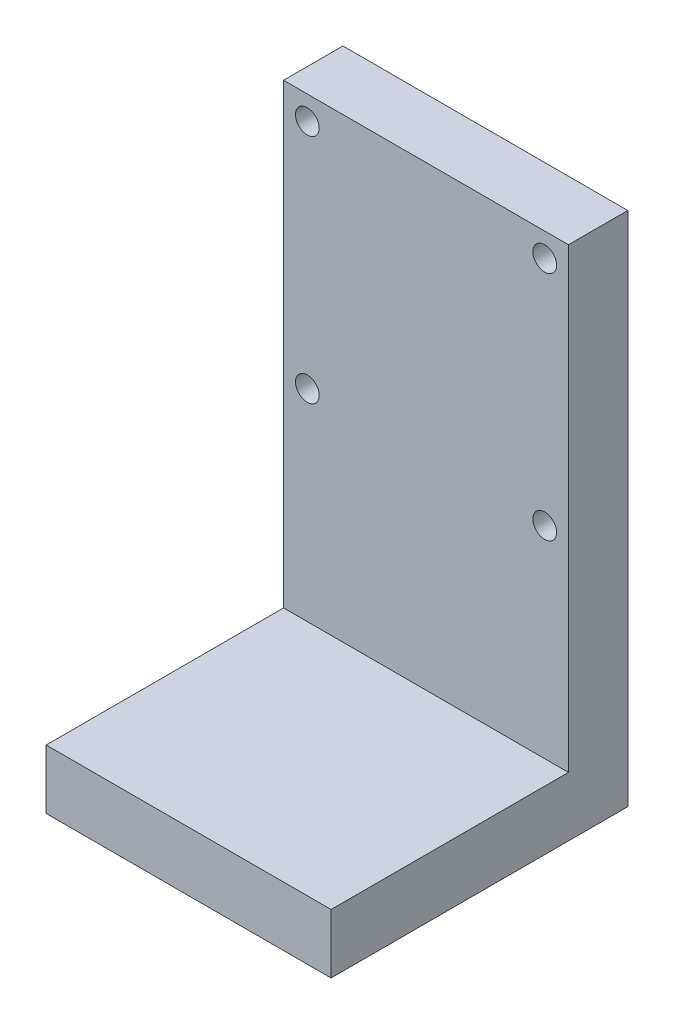
SolidWorks part; units mm, degrees
ref_plane "Front Plane" through (0, 0, 0) normal (0, 0, 1) x (1, 0, 0)
ref_plane "Top Plane" through (0, 0, 0) normal (0, 1, 0) x (1, 0, 0)
ref_plane "Right Plane" through (0, 0, 0) normal (1, 0, 0) x (0, 0, -1)
sketch "Sketch3" plane through (0, 0, 0) normal (0, 0, 1) x (1, 0, 0)
  line L0 (-24, -23.5) -> (-24, -63.5)
  line L1 (-24, 23.5) -> (24, 23.5)
  line L2 (-24, 23.5) -> (-24, -23.5)
  line L3 (-24, -23.5) -> (24, -23.5)
  line L4 (24, 23.5) -> (24, -23.5)
  line L5 (0, -23.5) -> (0, 23.5) construction
  line L6 (-24, 0) -> (24, 0) construction
  line L7 (-20, 19.5) -> (20, 19.5) construction
  line L8 (-20, 19.5) -> (-20, -19.5) construction
  line L9 (-20, -19.5) -> (20, -19.5) construction
  line L10 (20, 19.5) -> (20, -19.5) construction
  line L11 (0, -19.5) -> (0, 19.5) construction
  line L12 (-20, 0) -> (20, 0) construction
  line L13 (-24, -63.5) -> (24, -63.5)
  line L14 (24, -63.5) -> (24, -23.5)
  line L15 (-24, -53.5) -> (24, -53.5)
  circle A0 centre (20, 19.5) radius 2
  circle A1 centre (20, -19.5) radius 2
  circle A2 centre (-20, -19.5) radius 2
  circle A3 centre (-20, 19.5) radius 2
  point P0 (0, 0)
  point P4 (0, 0)
  dimension "D5" = 4
  dimension "D6" = 4
  dimension "D7" = 4
  dimension "D8" = 4
  dimension "D1" = 47
  dimension "D2" = 48
  dimension "D3" = 39
  dimension "D4" = 40
  dimension "D9" = 40
  dimension "D10" = 30
extrude "Boss-Extrude1" add sketch "Sketch3" along normal blind 10 contours L0 L15 L14 L3 | L4 L1 L2 L3 A3 A2 A1 A0 | L15 L0 L13 L14 region at (0, -38.5, 0) region at (0, 0, 0) region at (0, -58.5, 0)
extrude "Boss-Extrude2" add sketch "Sketch3<3>" along normal blind 50 contours L15 L0 L13 L14 region at (0, -58.5, 0)
sketch "Sketch3<3>" plane through (0, 0, 0) normal (0, 0, 1) x (1, 0, 0) same geometry as "Sketch3"
